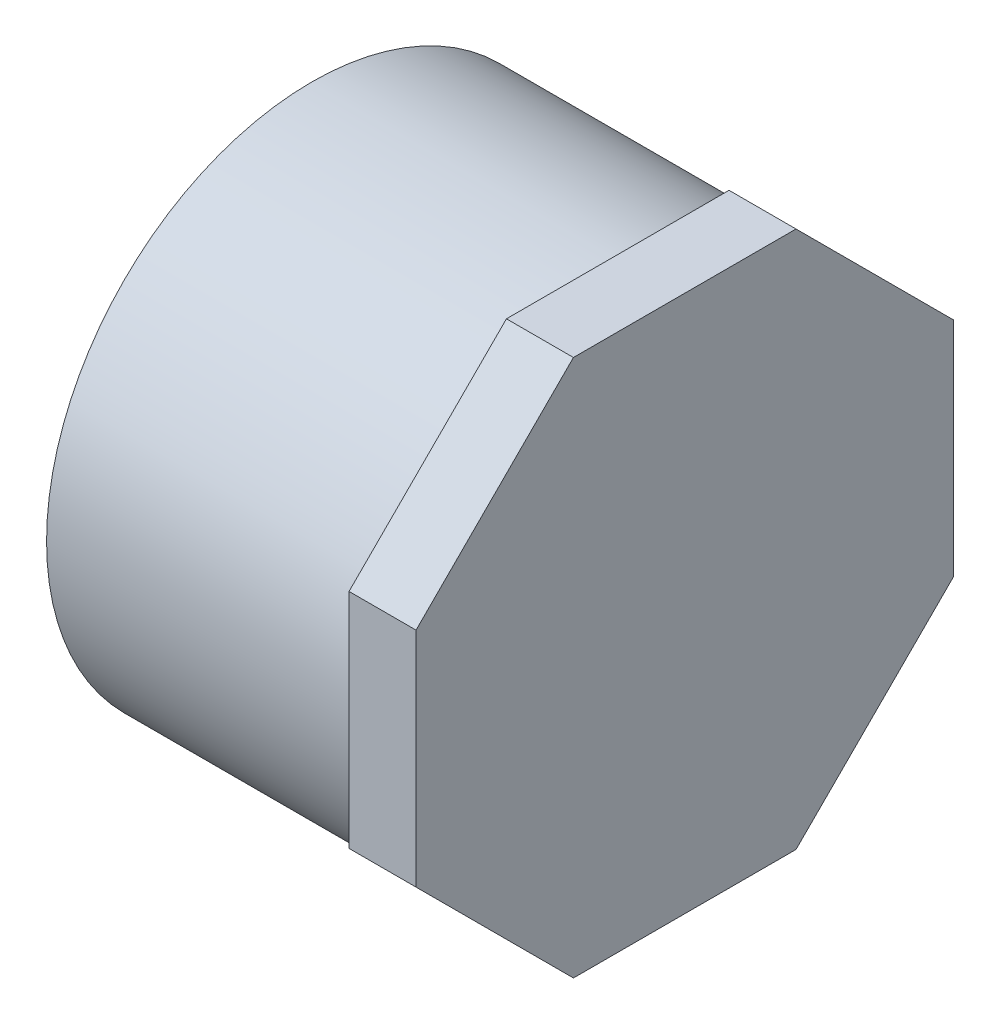
SolidWorks part; units mm, degrees
ref_plane "Front Plane" through (0, 0, 0) normal (0, 0, 1) x (1, 0, 0)
ref_plane "Top Plane" through (0, 0, 0) normal (0, 1, 0) x (1, 0, 0)
ref_plane "Right Plane" through (0, 0, 0) normal (1, 0, 0) x (0, 0, -1)
sketch "Sketch0" plane through (0, 0, 0) normal (0, 0, 1) x (1, 0, 0)
  line L2 (-21.209, 30.1625) -> (-21.209, -30.1625) construction
  line L3 (-21.209, 0) -> (21.209, 0) construction
  line L14 (13.589, 26.2509) -> (13.589, -26.2509) construction
  point P5 (13.589, 0)
  dimension "ID" = 52.5018
  dimension "L" = 42.418
  dimension "C" = 34.798
  dimension "Pipe OD" = 60.325
  dimension "R" = 7.62
  dimension "Wall Thickness" = 3.9116
sketch "Sketch1" plane through (0, 0, 0) normal (0, 0, 1) x (1, 0, 0)
  line L0 (-21.209, -30.1625) -> (21.209, -30.1625)
  line L1 (-21.209, 0) -> (21.209, 0) construction
  line L3 (21.209, 0) -> (13.589, 0)
  line L4 (13.589, -26.2509) -> (-21.209, -26.2509)
  line L5 (-21.209, -26.2509) -> (-21.209, -30.1625)
  line L6 (-21.209, 30.1625) -> (-21.209, -30.1625) construction
  line L7 (21.209, 0) -> (21.209, -30.1625)
  line L10 (13.589, 0) -> (13.589, -26.2509)
revolve "Revolve1" add sketch "Sketch1" angle 360 about L1
sketch "Sketch2" plane through (21.209, 0, 0) normal (1, 0, 0) x (0, 0, -1)
  line L0 (0, 35.2869) -> (0, 0) construction
  line L1 (0, 35.2869) -> (-30.5594, 17.6435) construction
  line L2 (-30.5594, 17.6435) -> (-30.5594, -17.6435) construction
  line L3 (-30.5594, -17.6435) -> (0, -35.2869) construction
  line L4 (0, -35.2869) -> (30.5594, -17.6435) construction
  line L5 (30.5594, -17.6435) -> (30.5594, 17.6435) construction
  line L6 (30.5594, 17.6435) -> (0, 35.2869) construction
  line L8 (-12.6581, 30.5594) -> (-30.5594, 12.6581)
  line L9 (-30.5594, 12.6581) -> (-30.5594, -12.6581)
  line L10 (-30.5594, -12.6581) -> (-12.6581, -30.5594)
  line L11 (-12.6581, -30.5594) -> (12.6581, -30.5594)
  line L12 (12.6581, -30.5594) -> (30.5594, -12.6581)
  line L13 (30.5594, -12.6581) -> (30.5594, 12.6581)
  line L14 (30.5594, 12.6581) -> (12.6581, 30.5594)
  line L15 (12.6581, 30.5594) -> (-12.6581, 30.5594)
  circle A0 centre (0, 0) radius 30.1625 construction
  circle A1 centre (0, 0) radius 30.1625
  circle A2 centre (0, 0) radius 30.5594 construction
  circle A3 centre (0, 0) radius 30.5594 construction
  dimension "D1" = 61.1187
extrude "Boss-Extrude1" add sketch "Sketch2" against normal up to vertex (7.62 mm away) up to point (13.589, 0, 0)
other "CPoint1" parameters "Diameter"=50.8, "StubLength"=228.6
ref_axis "Axis1" through (3.589, 0, 0) along (1, 0, 0)
other "RPoint1"
ref_axis "Axis of Rotation" through (13.589, 0, 0) along (-1, 0, 0)
